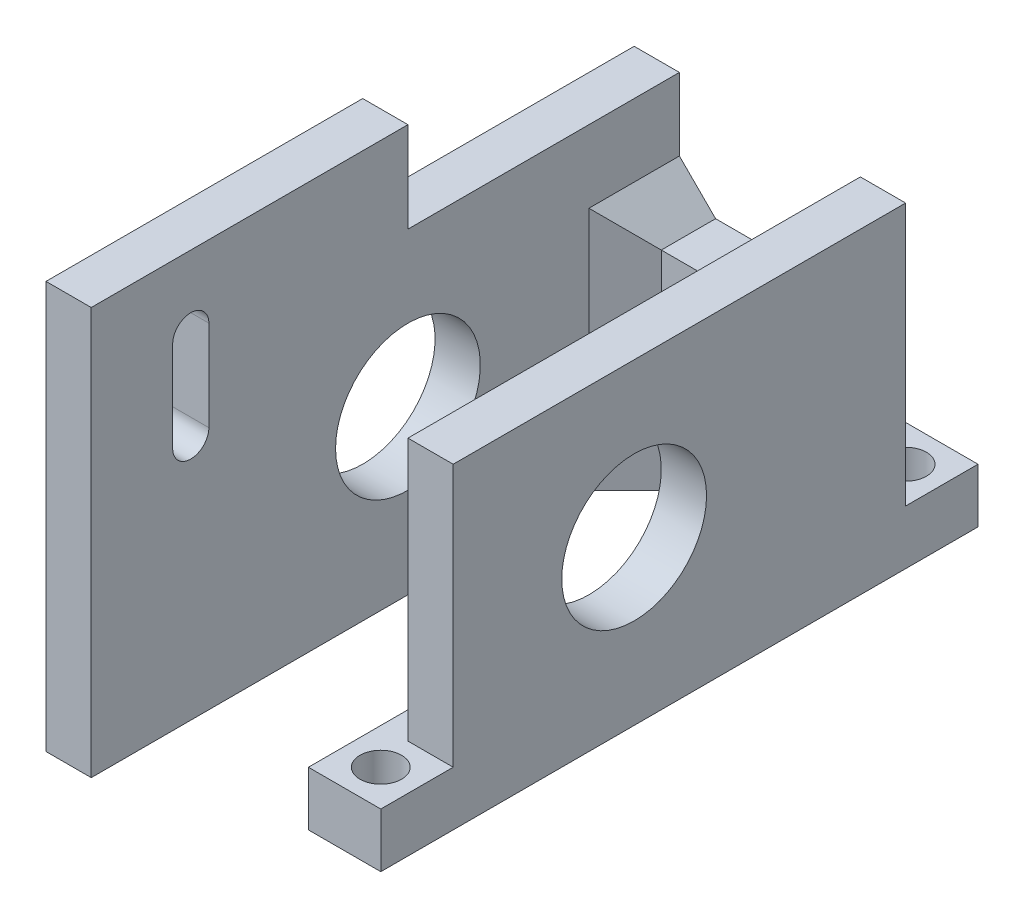
SolidWorks part; units mm, degrees
ref_plane "Plan de face" through (0, 0, 0) normal (0, 0, 1) x (1, 0, 0)
ref_plane "Plan de dessus" through (0, 0, 0) normal (0, 1, 0) x (1, 0, 0)
ref_plane "Plan de droite" through (0, 0, 0) normal (1, 0, 0) x (0, 0, -1)
sketch "Esquisse1" plane through (0, 0, 0) normal (0, 1, 0) x (1, 0, 0)
  line L8 (-23, 9) -> (-23, -41)
  line L9 (-18, 9) -> (-23, 9)
  line L28 (-23, -41) -> (-18, -41)
  line L30 (-18, -41) -> (-18, 3)
  line L31 (7, 3) -> (7, -41)
  line L32 (7, -41) -> (2, -41)
  line L33 (2, -41) -> (2, 3)
  line L35 (-18, 9) -> (2, 9)
  line L38 (-18, 3) -> (2, 3)
  line L39 (-23, -41) -> (-31, -41)
  line L40 (-31, -41) -> (-31, -33)
  line L45 (7, 9) -> (7, 3)
  line L46 (7, 3) -> (-23, 3) construction
  line L47 (-23, 3) -> (-23, 9)
  line L50 (-31, -33) -> (-23, -33)
  line L51 (2, 9) -> (7, 9)
  line L55 (-31, -33) -> (-23, -41) construction
  line L56 (-23, -33) -> (-31, -41) construction
  line L57 (-23, 9) -> (-31, 9)
  line L58 (7, 9) -> (7, 17)
  line L59 (7, 17) -> (-1, 17)
  line L60 (-1, 17) -> (-1, 9)
  line L61 (-1, 9) -> (7, 17) construction
  line L62 (-1, 17) -> (7, 9) construction
  line L63 (7, -41) -> (7, -49)
  line L64 (7, -49) -> (-1, -49)
  line L65 (-1, -49) -> (-1, -37)
  line L66 (-1, -37) -> (2, -37)
  line L67 (7, -49) -> (-1, -41) construction
  line L68 (-1, -41) -> (-1, -49) construction
  line L69 (7, -41) -> (-1, -49) construction
  line L70 (-31, 9) -> (-31, 1)
  line L71 (-31, 1) -> (-23, 1)
  line L72 (-31, 9) -> (-23, 1) construction
  line L73 (-23, 1) -> (-23, 9) construction
  line L74 (-31, 1) -> (-23, 9) construction
  circle A8 centre (3, 13) radius 2.3
  circle A10 centre (3, -45) radius 2.3
  circle A11 centre (-27, -37) radius 2.3
  circle A12 centre (-27, 5) radius 2.3
extrude "Boss.-Extru.1" add sketch "Esquisse1" along normal blind 35 contours L46 | L46 L9 | L46 L35 | L51 L46 region at (-20.5, 0, -8.4169)
extrude "Boss.-Extru.7" add sketch "Esquisse1<6>" along normal blind 8 contours L28 region at (-20.5, 0, -8.4169)
sketch "Esquisse1<6>" plane through (0, 0, 0) normal (0, 1, 0) x (1, 0, 0) same geometry as "Esquisse1"
extrude "Boss.-Extru.8" add sketch "Esquisse1<8>" along normal blind 6 contours L59 L60 L35 L51 L58 A8 | L30 L28 L40 | L66 L65 L64 L63 L32 L33 A10 | L70 L71 L8 L57 A12 | L50 L40 L39 L8 A11 region at (-23.1131, 0, -6) region at (-0.8869, 0, -13) region at (-23.1131, 0, 37) region at (6.8558, 0, 45)
sketch "Esquisse1<8>" plane through (0, 0, 0) normal (0, 1, 0) x (1, 0, 0) same geometry as "Esquisse1"
sketch "Esquisse6" plane through (0, 0, 0) normal (0, -1, 0) x (1, 0, 0)
  line L0 (-18, -3) -> (-14, -3)
  line L1 (-18, -3) -> (2, -3) construction
  line L2 (-18, -3) -> (-18, 1)
  line L3 (-18, 41) -> (-18, -3) construction
  line L4 (-18, 1) -> (-14, -3)
  line L5 (2, -3) -> (-2, -3)
  line L6 (-2, -3) -> (2, 1)
  line L7 (2, 37) -> (2, -3) construction
  line L8 (2, 1) -> (2, -3)
extrude "Boss.-Extru.9" add sketch "Esquisse6" against normal blind 35
sketch "Esquisse7" plane through (0, 0, -9) normal (0, 0, -1) x (-1, 0, 0)
  line L0 (-7, 35) -> (-2, 35) construction
  line L3 (18, 23) -> (14, 23) construction
  line L8 (-2, 23) -> (2, 23) construction
  line L9 (2, 23) -> (-2, 23) construction
  line L10 (-2, 23) -> (-2, 27) construction
  line L14 (-2, 35) -> (18, 35)
  line L16 (18, 23) -> (18, 27) construction
  line L17 (2, 23) -> (14, 23)
  line L18 (-2, 27) -> (2, 23)
  line L24 (-2, 27) -> (-2, 35)
  line L25 (18, 23) -> (18, 35)
  line L26 (18, 27) -> (14, 23)
  line M8 (23, 35) -> (-7, 35)
extrude "Enlèv. mat.-Extru.5" cut sketch "Esquisse7" against normal blind 35 contours L18 M8 region at (-8, 29.3333, -9)
sketch "Esquisse8" plane through (-23, 0, 0) normal (-1, 0, 0) x (0, 0, 1)
  circle A0 centre (21, 18) radius 8
extrude "Enlèv. mat.-Extru.6" cut sketch "Esquisse8" against normal blind 50 contours A0 region at (-23, 18, 21)
sketch "Esquisse9" plane through (-23, 0, 0) normal (-1, 0, 0) x (0, 0, 1)
  line L1 (56, 0) -> (56, 45)
  line L6 (21, 18) -> (21, 45) construction
  line L7 (21, 45) -> (21, 35)
  line L8 (21, 45) -> (56, 45)
  line L9 (21, 35) -> (41, 35)
  line L10 (56, 0) -> (41, 0)
  line L11 (41, 0) -> (41, 35)
extrude "Boss.-Extru.10" add sketch "Esquisse9" against normal blind 5
sketch "Esquisse10" plane through (-23, 0, 0) normal (-1, 0, 0) x (0, 0, 1)
  line L1 (-1, 0) -> (33, 0) construction
  line L2 (21, 0) -> (45, 0) construction
  line L3 (45, 0) -> (45, 45) construction
  line L4 (56, 45) -> (21, 45) construction
  line L5 (45, 45) -> (45, 37) construction
  line L6 (43, 37) -> (43, 27)
  line L7 (43, 27) -> (47, 27) construction
  line L8 (47, 27) -> (47, 37)
  circle A0 centre (45, 37) radius 2
  circle A1 centre (45, 27) radius 2
extrude "Enlèv. mat.-Extru.7" cut sketch "Esquisse10" against normal blind 5 contours A1 | A1 L8 A0 L6 | A0 region at (-23, 32, 45) region at (-23, 27, 45)
